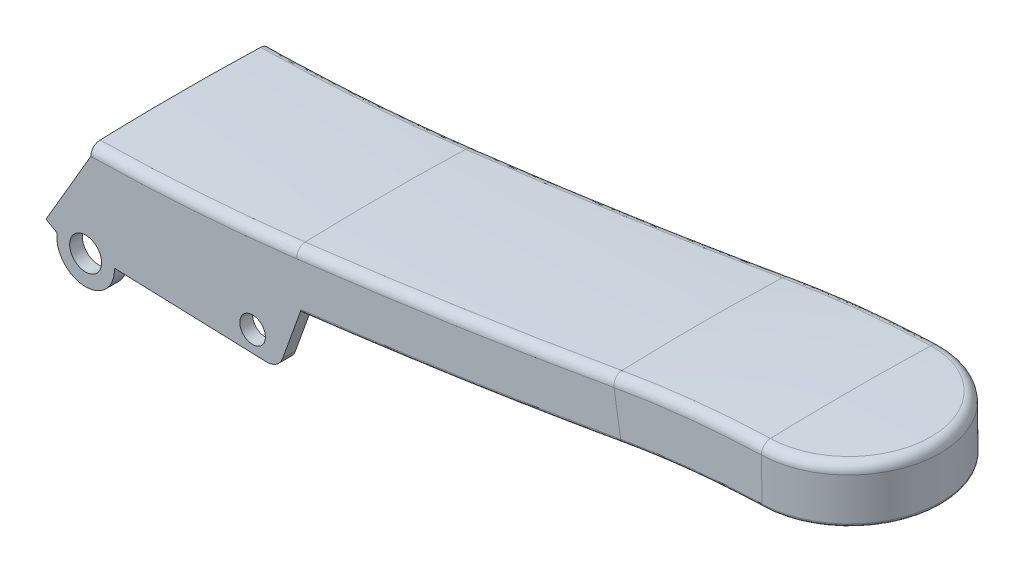
SolidWorks part; units mm, degrees
material "Ferro fundido cinza (SN)"
ref_plane "Plano frontal" through (0, 0, 0) normal (0, 0, 1) x (1, 0, 0)
ref_plane "Plano superior" through (0, 0, 0) normal (0, 1, 0) x (1, 0, 0)
ref_plane "Plano direito" through (0, 0, 0) normal (1, 0, 0) x (0, 0, -1)
sketch "Esboço1" plane through (0, 0, 0) normal (0, 0, 1) x (1, 0, 0)
  arc A0 (0, 0) -> (33, 2.2682) centre (-5.3127, 318.4885) ccw
  arc A1 (33, 2.2682) -> (83, 9.6978) centre (-79.8486, 933.6841) ccw
  arc A2 (83, 9.6978) -> (105, 12) centre (110.3739, -145.6188) cw
  point P8 (91.2779, 20.1794)
  point P9 (84.9557, 13.358)
  point P10 (37.3725, 3.2092)
  point P11 (88, 10.7711)
  point P12 (88, 8.9759)
  dimension "D1" = 105
  dimension "D2" = 22
  dimension "D3" = 33
  dimension "D4" = 12
sketch "Esboço2" plane through (0, 0, 0) normal (1, 0, 0) x (0, 0, -1)
  line L0 (-14, 7.4427) -> (-14, 0.8944)
  line L1 (0, 9.1363) -> (0, 8.064) construction
  line L2 (0, 9.6978) -> (0, 2.2682) construction
  line L3 (-13, 6.736) -> (-13, 0.8944)
  line L4 (13, 6.736) -> (13, 0.8944)
  line L5 (14, 7.4427) -> (14, 0.8944)
  arc A0 (12.5464, 8.942) -> (-12.5464, 8.942) centre (0, -396.1075) ccw
  arc A1 (-14, 0.8944) -> (-13, 0.8944) centre (-13.5, 0.8944) ccw
  arc A2 (12.1183, 7.6759) -> (0, 8.064) centre (-0.0267, -182.1722) ccw
  arc A3 (-13, 6.736) -> (-12.1183, 7.6759) centre (-12.0582, 6.736) cw
  arc A4 (-12.1183, 7.6759) -> (0, 8.064) centre (0.0267, -182.1722) cw
  arc A5 (13, 6.736) -> (12.1183, 7.6759) centre (12.0582, 6.736) ccw
  arc A6 (14, 0.8944) -> (13, 0.8944) centre (13.5, 0.8944) cw
  arc A7 (-12.5464, 8.942) -> (-14, 7.4427) centre (-12.5, 7.4427) ccw
  arc A8 (14, 7.4427) -> (12.5464, 8.942) centre (12.5, 7.4427) ccw
  point P10 (-12, 6.6745)
  point P18 (0, 0)
  point P19 (13.031, 7.7539)
  point P20 (-12, 6.3053)
  point P21 (-11.5666, 7.9886)
  point P22 (-12, 5.9402)
  point P23 (-11.8524, 7.7482)
  point P24 (-12, 6.3836)
  point P25 (-12, 5.718)
  point P26 (-10.3386, 7.7181)
  point P27 (0, 0)
  point P34 (-14, 8.8944)
  point P37 (14, 8.8944)
  point P38 (0, 0)
  point P39 (-13, 6.736)
  point P40 (0, 0)
  dimension "D1" = 1.5
  dimension "D3" = 0.5
  dimension "D2" = 8
sweep "Varredura1" add profiles "Esboço2" path "Esboço1"
sketch "Esboço3" plane through (105.177, 1.8304, 0) normal (0.9998, 0.0174, 0) x (0, 0, -1)
  line L0 (0, 19.3074) -> (0, -1.0381) construction
  line L1 (14, 17.6138) -> (14, 11.0655)
  line L2 (13, 11.0655) -> (13, 16.9071)
  line L3 (0, 19.3074) -> (0, 18.2351)
  arc A0 (12.5464, 19.1131) -> (-12.5464, 19.1131) centre (0, -385.9364) ccw construction
  arc A1 (12.5464, 19.1131) -> (14, 17.6138) centre (12.5, 17.6138) cw
  arc A2 (0, 19.3074) -> (12.5464, 19.1131) centre (0, -385.9364) cw
  arc A3 (14, 11.0655) -> (13, 11.0655) centre (13.5, 11.0655) cw
  arc A4 (13, 11.0655) -> (14, 11.0655) centre (13.5, 11.0655) ccw construction
  arc A5 (13, 16.9071) -> (12.1183, 17.847) centre (12.0582, 16.9071) ccw
  arc A6 (12.1183, 17.847) -> (0, 18.2351) centre (-0.0267, -172.0011) ccw
revolve "Revolução1" add sketch "Esboço3" angle 180 about L0
sketch "Esboço6" plane through (0, 0, 14) normal (0, 0, 1) x (1, 0, 0)
  line L0 (0, 7.4427) -> (-7, -4.5573)
  line L1 (-7, -4.5573) -> (-5.2724, -5.565)
  line L2 (3.685, -5.8388) -> (27.4648, -6.6448)
  line L3 (29.9994, -4.9263) -> (32.9072, 3.1577)
  line L4 (32.9072, 3.1577) -> (32.2282, 9.6708)
  arc A0 (-5.2724, -5.565) -> (3.685, -5.8388) centre (-0.8064, -6.1167) ccw
  arc A1 (27.4648, -6.6448) -> (29.9994, -4.9263) centre (27.5528, -4.0463) ccw
  arc A2 (32.2282, 9.6708) -> (0, 7.4427) centre (-5.2091, 316.991) cw
  point P12 (0, 0)
  point P13 (0, 0)
  point P15 (0, 0)
  point P19 (0, 0)
  point P21 (-1.0688, -6.0342)
  point P22 (-1.1739, -5.6741)
  point P23 (-1.7877, -5.7587)
  point P24 (1.7438, -6.6448)
  dimension "D1" = 12
  dimension "D3" = 2.6
  dimension "D5" = 4.5
  dimension "D2" = 2
  dimension "D4" = 18
  dimension "D6" = 7
extrude "Ressalto-extrusão1" add sketch "Esboço6" against normal blind 2
mirror "Espelhar1" about plane through (0, 0, 0) normal (0, 0, 1) of "Ressalto-extrusão1"
sketch "Esboço7" plane through (0, 0, 14) normal (0, 0, 1) x (1, 0, 0)
  circle A0 centre (-0.8064, -6.1167) radius 2.5
  arc A1 (-5.2724, -5.565) -> (3.685, -5.8388) centre (-0.8064, -6.1167) ccw construction
  point P2 (0, 0)
extrude "Corte-extrusão1" cut sketch "Esboço7" against normal through all
sketch "Esboço8" plane through (0, 0, 14) normal (0, 0, 1) x (1, 0, 0)
  line L0 (3.685, -5.8388) -> (27.4648, -6.6448) construction
  circle A0 centre (25.3072, -3.3698) radius 2
  dimension "D1" = 4
  dimension "D2" = 7.6
  dimension "D3" = 3.2
extrude "Corte-extrusão2" cut sketch "Esboço8" against normal through all
